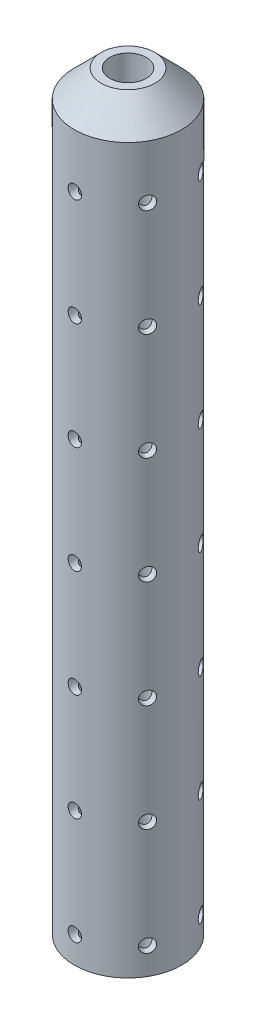
SolidWorks part; units mm, degrees
ref_plane "Front Plane" through (0, 0, 0) normal (0, 0, 1) x (1, 0, 0)
ref_plane "Top Plane" through (0, 0, 0) normal (0, 1, 0) x (1, 0, 0)
ref_plane "Right Plane" through (0, 0, 0) normal (1, 0, 0) x (0, 0, -1)
sketch "Sketch1" plane through (0, 0, 0) normal (0, 1, 0) x (1, 0, 0)
  line L1 (3.6955, 0) -> (1.8478, 3.2004)
  line L2 (1.8478, 3.2004) -> (-1.8478, 3.2004)
  line L3 (-1.8478, 3.2004) -> (-3.6955, 0)
  line L4 (-3.6955, 0) -> (-1.8478, -3.2004)
  line L5 (-1.8478, -3.2004) -> (1.8478, -3.2004)
  line L6 (1.8478, -3.2004) -> (3.6955, 0)
  circle A0 centre (0, 0) radius 3.2004 construction
  circle A1 centre (0, 0) radius 6.35
  dimension "D1" = 6.4008
  dimension "D2" = 12.7
extrude "Boss-Extrude1" add sketch "Sketch1" along normal blind 85.725
sketch "Sketch2" plane through (0, 85.725, 0) normal (0, 1, 0) x (1, 0, 0)
  circle A1 centre (0, 0) radius 2.159
  circle A2 centre (0, 0) radius 6.35
  circle A3 centre (0, 0) radius 6.35
  dimension "D2" = 4.318
  dimension "D1" = 0
extrude "Boss-Extrude2" add sketch "Sketch2" along normal blind 3.175
chamfer "Chamfer1" distance 3.175 distance2 3.175 1 edges at (0, 88.9, 6.35)
sketch "Sketch4" plane through (0, 0, 0) normal (0, -1, 0) x (1, 0, 0)
  circle A0 centre (0, 4.7625) radius 0.7938
  dimension "D2" = 1.5875
  dimension "D1" = 4.7625
extrude "Cut-Extrude1" cut sketch "Sketch4" against normal blind 85.725
ref_plane "Plane1" through (0, 0, 12.7) normal (0, 0, 1) x (1, 0, 0)
sketch "Sketch3" plane through (0, 0, 12.7) normal (0, 0, 1) x (1, 0, 0)
  line L0 (-6.35, 85.725) -> (6.35, 85.725) construction
  line L1 (0, 79.375) -> (0, 66.675) construction
  circle A0 centre (0, 79.375) radius 0.7937
  circle A1 centre (0, 66.675) radius 0.7937
  circle A2 centre (0, 53.975) radius 0.7937
  circle A3 centre (0, 41.275) radius 0.7937
  circle A4 centre (0, 28.575) radius 0.7937
  circle A5 centre (0, 15.875) radius 0.7937
  circle A6 centre (0, 3.175) radius 0.7938
  dimension "D2" = 1.5875
  dimension "D1" = 6.35
  dimension "D4" = 12.7
  dimension "D3" = 7
extrude "Cut-Extrude2" cut sketch "Sketch3" against normal up to surface (7.9375 mm away) up to face at (0, 85.725, 3.9688)
pattern_circular "CirPattern1" count 6 over 360 about axis through (0, 88.9, 0) along (0, 1, 0) of "Cut-Extrude1", "Cut-Extrude2"
